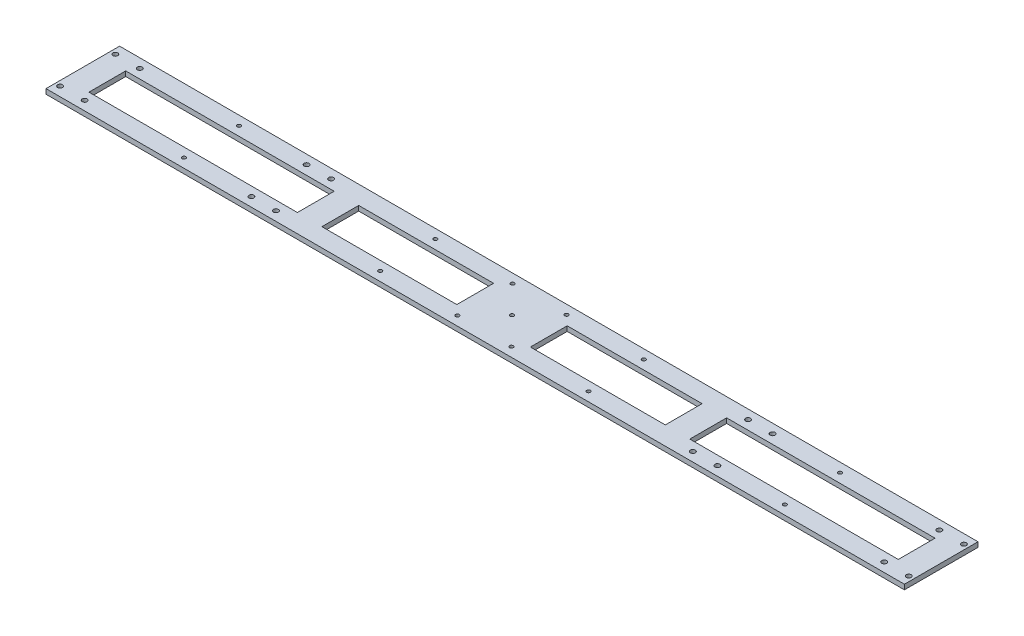
SolidWorks part; units mm, degrees
ref_plane "前视基准面" through (0, 0, 0) normal (0, 0, 1) x (1, 0, 0)
ref_plane "上视基准面" through (0, 0, 0) normal (0, 1, 0) x (1, 0, 0)
ref_plane "右视基准面" through (0, 0, 0) normal (1, 0, 0) x (0, 0, -1)
other "Configuration Table"
sketch "草图1" plane through (0, 0, 0) normal (0, 1, 0) x (1, 0, 0)
  line L1 (-350, -30) -> (350, -30)
  line L2 (-350, -30) -> (-350, 30)
  line L3 (-350, 30) -> (350, 30)
  line L4 (350, -30) -> (350, 30)
  line L5 (-350, -30) -> (350, 30) construction
  line L6 (-350, 30) -> (350, -30) construction
  line L7 (-140, -15) -> (140, -15)
  line L8 (-140, -15) -> (-140, 15)
  line L9 (-140, 15) -> (140, 15)
  line L10 (140, -15) -> (140, 15)
  line L11 (-140, -15) -> (140, 15) construction
  line L12 (-140, 15) -> (140, -15) construction
  point P0 (0, 0)
  point P6 (0, 0)
  dimension "D1" = 700
  dimension "D2" = 60
  dimension "D3" = 30
  dimension "D4" = 280
extrude "凸台-拉伸1" add sketch "草图1" along normal blind 4
sketch "草图2" plane through (0, 4, 0) normal (0, 1, 0) x (1, 0, 0)
  line L1 (-330, 15) -> (-160, 15)
  line L2 (-330, 15) -> (-330, -15)
  line L3 (-330, -15) -> (-160, -15)
  line L4 (-160, 15) -> (-160, -15)
  line L5 (140, 15) -> (-140, 15) construction
  line L6 (-140, -15) -> (140, -15) construction
  line L7 (-140, 15) -> (-140, -15) construction
  line L8 (-350, 30) -> (-350, -30) construction
  dimension "D1" = 20
  dimension "D2" = 20
extrude "切除-拉伸1" cut sketch "草图2" against normal blind 4
mirror "镜向1" about plane through (0, 0, 0) normal (1, 0, 0) of "切除-拉伸1"
sketch "草图3" plane through (0, 4, 0) normal (0, 1, 0) x (1, 0, 0)
  line L0 (350, 30) -> (-350, 30) construction
  line L2 (-350, 30) -> (-350, -30) construction
  circle A0 centre (-190, 22.5) radius 2
  circle A1 centre (-170, 22.5) radius 2
  circle A2 centre (-346, 22.5) radius 2
  circle A3 centre (-326, 22.5) radius 2
  point P6 (0, 0)
  dimension "D2" = 4
  dimension "D3" = 170
  dimension "D5" = 4
  dimension "D1" = 7.5
  dimension "D4" = 20
  dimension "D6" = 20
  dimension "D7" = 7.5
  dimension "D8" = 4
extrude "切除-拉伸2" cut sketch "草图3" against normal blind 4
mirror "镜向2" about plane through (0, 0, 0) normal (1, 0, 0) of "切除-拉伸2" second plane through (0, 0, 0) second plane normal (0, 0, 1)
sketch "草图4" plane through (0, 4, 0) normal (0, 1, 0) x (1, 0, 0)
  line L0 (140, 15) -> (-140, 15) construction
  line L1 (-30, -15) -> (30, -15)
  line L2 (-30, -15) -> (-30, 15)
  line L3 (-30, 15) -> (30, 15)
  line L4 (30, -15) -> (30, 15)
  line L5 (-30, -15) -> (30, 15) construction
  line L6 (-30, 15) -> (30, -15) construction
  point P0 (0, 0)
  point P7 (0, 0)
  dimension "D1" = 60
extrude "凸台-拉伸2" add sketch "草图4" against normal blind 4
sketch "草图5" plane through (0, 4, 0) normal (0, 1, 0) x (1, 0, 0)
  line L0 (-85, 22.5) -> (-85, 15) construction
  line L1 (-245, 22.5) -> (-245, 15) construction
  line L2 (-160, 15) -> (-330, 15) construction
  line L3 (-30, 15) -> (-140, 15) construction
  line L4 (-30, 15) -> (-30, -15) construction
  circle A0 centre (-245, 22.5) radius 1.5
  circle A1 centre (-85, 22.5) radius 1.5
  circle A2 centre (0, 0) radius 1.5
  circle A3 centre (-22, 22.5) radius 1.5
  point P10 (0, 0)
  point P13 (-255, 22.7641)
  point P14 (-83.489, 10.533)
  point P19 (0, 0)
  dimension "D1" = 3
  dimension "D2" = 7.5
  dimension "D3" = 8
extrude "切除-拉伸3" cut sketch "草图5" against normal blind 4
mirror "镜向3" about plane through (0, 0, 0) normal (0, 0, 1) of "切除-拉伸3" second plane through (0, 0, 0) second plane normal (1, 0, 0)
